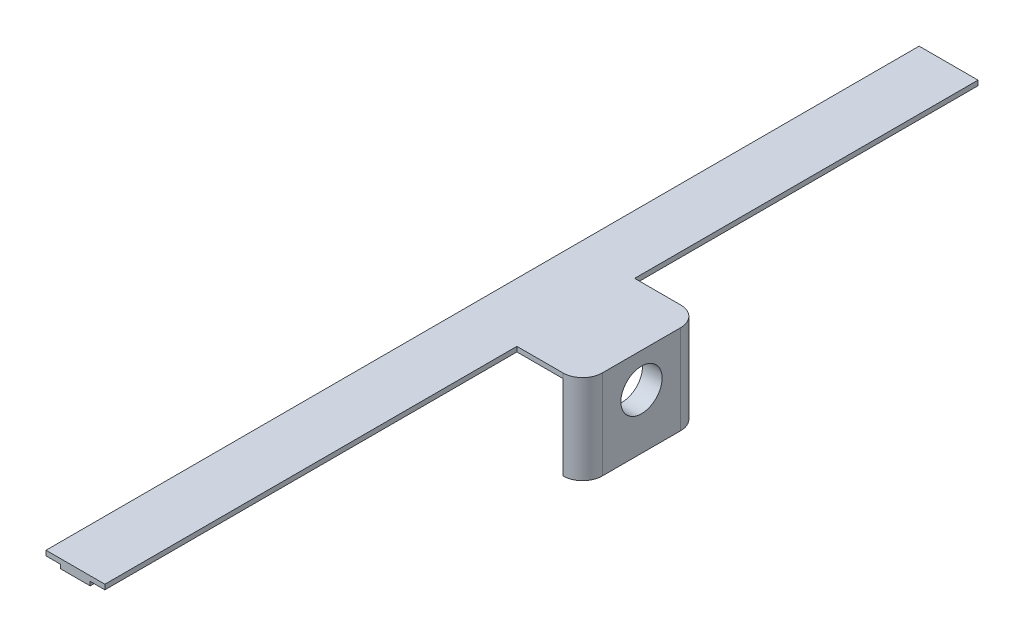
SolidWorks part; units mm, degrees
ref_plane "Front Plane" through (0, 0, 0) normal (0, 0, 1) x (1, 0, 0)
ref_plane "Top Plane" through (0, 0, 0) normal (0, 1, 0) x (1, 0, 0)
ref_plane "Right Plane" through (0, 0, 0) normal (1, 0, 0) x (0, 0, -1)
sketch "Sketch1" plane through (0, 0, 0) normal (0, 1, 0) x (1, 0, 0)
  line L1 (-1.5, 44.5) -> (1.5, 44.5)
  line L2 (-1.5, 44.5) -> (-1.5, -44.5)
  line L3 (-1.5, -44.5) -> (1.5, -44.5)
  line L4 (1.5, 44.5) -> (1.5, -44.5)
  line L5 (-1.5, 44.5) -> (1.5, -44.5) construction
  line L6 (-1.5, -44.5) -> (1.5, 44.5) construction
  point P0 (0, 0)
  dimension "D1" = 89
  dimension "D2" = 3
extrude "Boss-Extrude1" add sketch "Sketch1" along normal blind 0.4
sketch "Sketch2" plane through (0, 0.4, 0) normal (0, 1, 0) x (1, 0, 0)
  line L0 (3, 9.5) -> (3, 44.5)
  line L1 (-3, -44.5) -> (3, -44.5)
  line L2 (-3, -44.5) -> (-3, 44.5)
  line L3 (-3, 44.5) -> (3, 44.5)
  line L4 (3, -44.5) -> (3, -2.5)
  line L5 (-3, -44.5) -> (3, 44.5) construction
  line L6 (-3, 44.5) -> (3, -44.5) construction
  line L7 (3, 9.5) -> (9.7, 9.5)
  line L9 (3, -2.5) -> (9.7, -2.5)
  line L10 (9.7, 9.5) -> (9.7, -2.5)
  line L11 (1.5, -44.5) -> (1.5, 44.5) construction
  point P0 (0, 0)
  dimension "D1" = 6
  dimension "D2" = 35
  dimension "D3" = 12
  dimension "D4" = 8.2
extrude "Boss-Extrude2" add sketch "Sketch2" along normal blind 0.5
sketch "Sketch3" plane through (0, 0.4, 0) normal (0, -1, 0) x (1, 0, 0)
  line L0 (9.7, -9.5) -> (3, -9.5) construction
  line L1 (9.7, 2.5) -> (7.7, 2.5)
  line L2 (9.7, 2.5) -> (9.7, -9.5)
  line L3 (9.7, -9.5) -> (7.7, -9.5)
  line L4 (7.7, 2.5) -> (7.7, -9.5)
  dimension "D1" = 2
extrude "Boss-Extrude3" add sketch "Sketch3" along normal blind 8.6
fillet "Fillet1" radius 2 2 edges at (9.7, -3.65, 2.5) (9.7, -3.65, -9.5)
sketch "Sketch4" plane through (9.7, 0, 0) normal (1, 0, 0) x (0, 0, -1)
  line L0 (-0.5, 0.9) -> (7.5, 0.9) construction
  circle A0 centre (3.5, -2.6) radius 2.1
  point P5 (3.5, 0.9)
  dimension "D2" = 4.2
  dimension "D1" = 3.5
extrude "Cut-Extrude1" cut sketch "Sketch4" against normal through all
